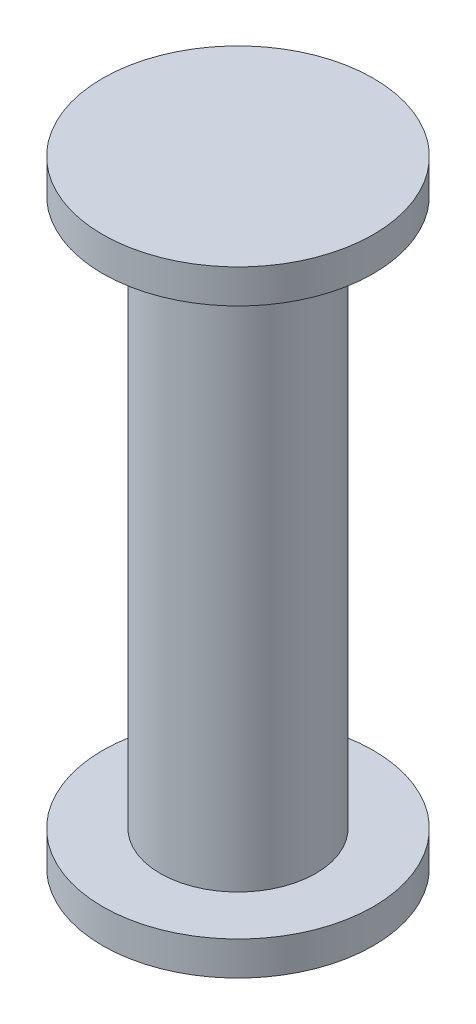
SolidWorks part; units mm, degrees
ref_plane "Front Plane" through (0, 0, 0) normal (0, 0, 1) x (1, 0, 0)
ref_plane "Top Plane" through (0, 0, 0) normal (0, 1, 0) x (1, 0, 0)
ref_plane "Right Plane" through (0, 0, 0) normal (1, 0, 0) x (0, 0, -1)
sketch "Sketch1" plane through (0, 0, 0) normal (0, 1, 0) x (1, 0, 0)
  circle A0 centre (0, 0) radius 2.3
  dimension "D1" = 4.6
extrude "Boss-Extrude1" add sketch "Sketch1" along normal blind 18.2
ref_plane "Plane1" through (0, 9.1, 0) normal (0, 1, 0) x (1, 0, 0)
sketch "Sketch2" plane through (0, 9.1, 0) normal (0, 1, 0) x (1, 0, 0)
  circle A0 centre (0, 0) radius 2.3
  circle A1 centre (0, 0) radius 4
  circle A2 centre (0, 0) radius 2.3 construction
  dimension "D1" = 8
extrude "Boss-Extrude2" add sketch "Sketch2" against normal blind 1 from surface starting at face at (0, 18.2, 2.3)
extrude "Boss-Extrude3" add sketch "Sketch2<3>" along normal blind 1 from surface starting at face at (0, 0, 2.3)
sketch "Sketch2<3>" plane through (0, 9.1, 0) normal (0, 1, 0) x (1, 0, 0) same geometry as "Sketch2"
